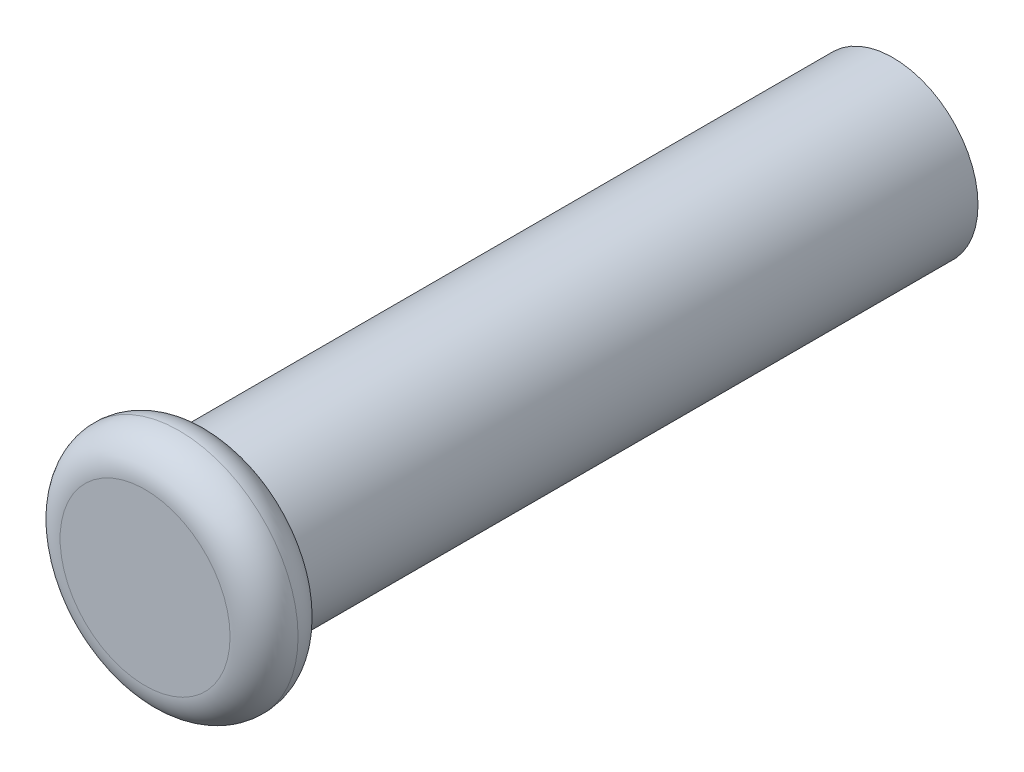
SolidWorks part; units mm, degrees
ref_plane "前视基准面" through (0, 0, 0) normal (0, 0, 1) x (1, 0, 0)
ref_plane "上视基准面" through (0, 0, 0) normal (0, 1, 0) x (1, 0, 0)
ref_plane "右视基准面" through (0, 0, 0) normal (1, 0, 0) x (0, 0, -1)
sketch "草图1" plane through (0, 0, 0) normal (0, 0, 1) x (1, 0, 0)
  circle A0 centre (0, 0) radius 2.5
  dimension "D1" = 5
extrude "凸台-拉伸1" add sketch "草图1" along normal blind 20
sketch "草图2" plane through (0, 0, 20) normal (0, 0, 1) x (1, 0, 0)
  circle A0 centre (0, 0) radius 3.5
  dimension "D1" = 7
extrude "凸台-拉伸2" add sketch "草图2" along normal blind 2
fillet "圆角2" radius 1 2 edges at (3.5, 0, 22) (3.5, 0, 20)
